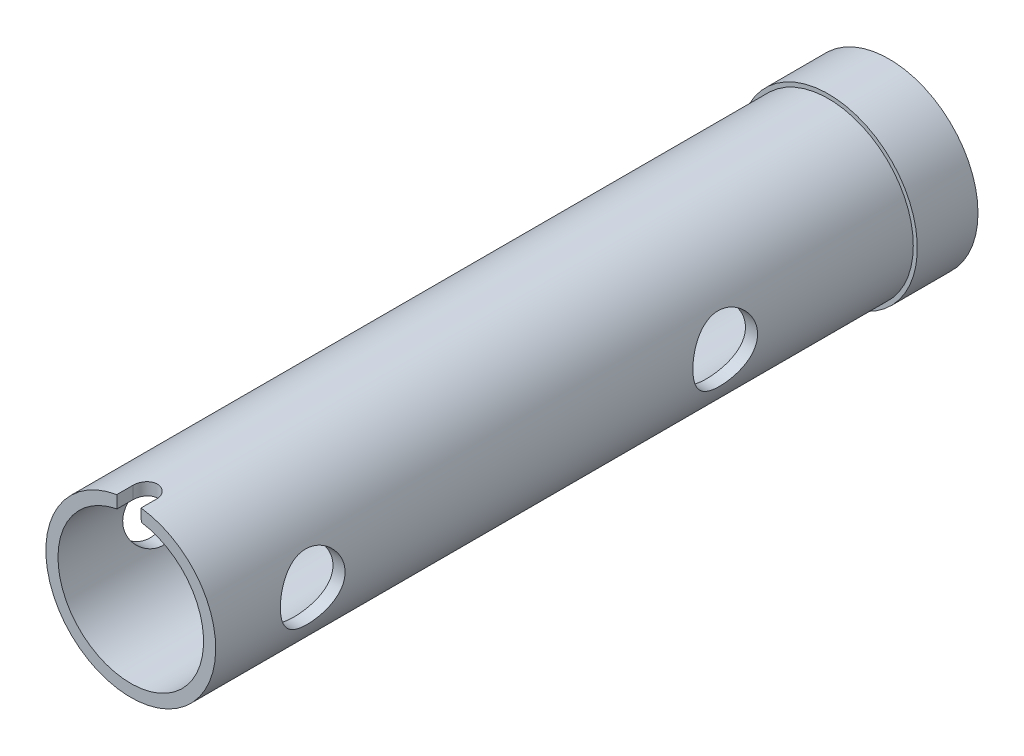
SolidWorks part; units mm, degrees
ref_plane "前视基准面" through (0, 0, 0) normal (0, 0, 1) x (1, 0, 0)
ref_plane "上视基准面" through (0, 0, 0) normal (0, 1, 0) x (1, 0, 0)
ref_plane "右视基准面" through (0, 0, 0) normal (1, 0, 0) x (0, 0, -1)
sketch "草图1" plane through (0, 0, 0) normal (0, 0, 1) x (1, 0, 0)
  circle A2 centre (-4.9354, -158.5614) radius 9
  circle A3 centre (-4.9354, -158.5614) radius 11
extrude "凸台-拉伸1" add sketch "草图1" along normal up to surface (7.5 mm away)
sketch "草图3" plane through (0, 0, 7.5) normal (0, 0, 1) x (1, 0, 0)
  circle A0 centre (-4.9354, -158.5614) radius 10.5
  circle A1 centre (-4.9354, -158.5614) radius 9
extrude "凸台-拉伸2" add sketch "草图3" along normal blind 86.25
ref_axis "基准轴1" through (-4.9354, -158.5614, 91.9449) along (0, 0, -1)
ref_plane "基准面1" through (-8.503, -0.1915, 0) normal (0.9997, 0.0225, 0) x (0, 0, -1)
sketch "草图4" plane through (-8.503, -0.1915, 0) normal (0.9997, 0.0225, 0) x (0, 0, -1)
  line L0 (-93.75, -149.41) -> (-93.75, -167.41) construction
  line L1 (-93.75, -149.41) -> (-93.75, -167.41) construction
  line L2 (-93.75, -158.41) -> (-81.9274, -158.41) construction
  circle A0 centre (-81.75, -158.41) radius 4
  circle A1 centre (-30.75, -158.41) radius 4
  dimension "D1" = 8
  dimension "D4" = 63
  dimension "D5" = 8
  dimension "D2" = 0
  dimension "D3" = 12
extrude "切除-拉伸1" cut sketch "草图4" against normal blind 86.25 and the other way blind 86.25
ref_plane "基准面2" through (3.5676, -158.3698, 0) normal (-0.0225, 0.9997, 0) x (0.9997, 0.0225, 0)
sketch "草图5" plane through (3.5676, -158.3698, 0) normal (-0.0225, 0.9997, 0) x (0.9997, 0.0225, 0)
  line L0 (-19.0052, -93.75) -> (1.9948, -93.75) construction
  line L1 (-19.0052, -93.75) -> (1.9948, -93.75) construction
  line L2 (-8.5052, -93.75) -> (-8.5052, -68.3861) construction
  line L3 (-8.5052, -93.75) -> (-8.5052, -91.75) construction
  line L4 (-10.0052, -93.75) -> (-10.0052, -91.75)
  line L5 (-7.0052, -93.75) -> (-7.0052, -91.75)
  arc A0 (-10.0052, -93.75) -> (-7.0052, -93.75) centre (-8.5052, -93.75) ccw
  arc A1 (-7.0052, -91.75) -> (-10.0052, -91.75) centre (-8.5052, -91.75) ccw
  point P8 (-8.5052, -92.75)
extrude "切除-拉伸2" cut sketch "草图5" along normal blind 35.25
